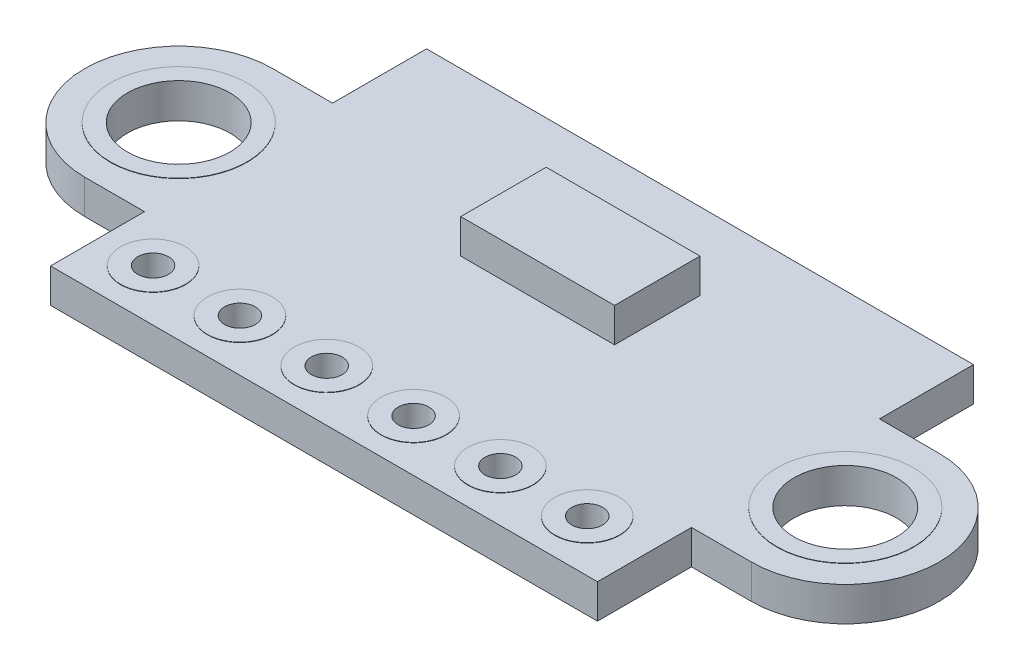
SolidWorks part; units mm, degrees
ref_plane "Front" through (0, 0, 0) normal (0, 0, 1) x (1, 0, 0)
ref_plane "Top" through (0, 0, 0) normal (0, 1, 0) x (1, 0, 0)
ref_plane "Right" through (0, 0, 0) normal (1, 0, 0) x (0, 0, -1)
sketch "Эскиз1" plane through (0, 0, 0) normal (0, 1, 0) x (1, 0, 0)
  line L0 (-38.6022, 0) -> (38.6022, 0) construction
  line L1 (8, -5.5) -> (-8, -5.5)
  line L2 (8, -5.5) -> (8, 5.5) construction
  line L3 (8, 5.5) -> (-8, 5.5)
  line L4 (-8, -5.5) -> (-8, 5.5) construction
  line L5 (8, -5.5) -> (-8, 5.5) construction
  line L6 (8, 5.5) -> (-8, -5.5) construction
  line L7 (-8, 5.5) -> (-8, 2.75)
  line L8 (0, -16.638) -> (0, 16.638) construction
  line L9 (-9.75, 2.75) -> (-8, 2.75)
  line L10 (-8, -5.5) -> (-8, -2.75)
  line L11 (-9.75, -2.75) -> (-8, -2.75)
  line L12 (9.75, -2.75) -> (8, -2.75)
  line L13 (8, -5.5) -> (8, -2.75)
  line L14 (8, 5.5) -> (8, 2.75)
  line L15 (9.75, 2.75) -> (8, 2.75)
  circle A0 centre (-9.75, 0) radius 1.5
  arc A1 (-9.75, 2.75) -> (-9.75, -2.75) centre (-9.75, 0) ccw
  circle A2 centre (9.75, 0) radius 1.5
  arc A3 (9.75, 2.75) -> (9.75, -2.75) centre (9.75, 0) cw
  circle A4 centre (-9.75, 0) radius 2
  circle A5 centre (9.75, 0) radius 2
  circle A6 centre (-6.5, -4) radius 0.45
  circle A7 centre (-6.5, -4) radius 0.95
  circle A8 centre (-3.96, -4) radius 0.95
  circle A9 centre (-3.96, -4) radius 0.45
  circle A10 centre (-1.42, -4) radius 0.95
  circle A11 centre (-1.42, -4) radius 0.45
  circle A12 centre (1.12, -4) radius 0.95
  circle A13 centre (1.12, -4) radius 0.45
  circle A14 centre (3.66, -4) radius 0.95
  circle A15 centre (3.66, -4) radius 0.45
  circle A16 centre (6.2, -4) radius 0.95
  circle A17 centre (6.2, -4) radius 0.45
  point P0 (0, 0)
  point P9 (0, 0)
  point P13 (0, 0)
  point P18 (-12.5, 0)
  point P25 (12.5, 0)
  dimension "D1" = 3
  dimension "D2" = 2.75
  dimension "D6" = 4
  dimension "D7" = 0.9
  dimension "D8" = 1.9
  dimension "D3" = 16
  dimension "D4" = 11
  dimension "D5" = 25
  dimension "D9" = 1.5
  dimension "D10" = 1.5
  dimension "D12" = 2.54
  dimension "D11" = 6
extrude "Бобышка-Вытянуть1" add sketch "Эскиз1" along normal blind 1 contours A0 | A2 | A6 | A9 | A11 | A13 | A15 | A17 | L7 L9 A1 L11 L10 L1 L13 L12 A3 L15 L14 L3 region at (-9.75, 0, 0) region at (9.75, 0, 0) region at (-6.5, 0, 4) region at (-3.96, 0, 4) region at (-1.42, 0, 4) region at (1.12, 0, 4) region at (3.66, 0, 4) region at (6.2, 0, 4)
extrude "Бобышка-Вытянуть2" add sketch "Эскиз1<3>" along normal blind 1.02 from offset 0.01 contours A4 A0 | A7 A6 | A8 A9 | A10 A11 | A12 A13 | A14 A15 | A16 A17 | A5 A2 region at (-11.6934, 0, 0) region at (7.8066, 0, 0) region at (-7.4231, 0, 4) region at (-4.8831, 0, 4) region at (-2.3431, 0, 4) region at (0.1969, 0, 4) region at (2.7369, 0, 4) region at (5.2769, 0, 4) offset against normal yes
sketch "Эскиз1<3>" plane through (0, 0, 0) normal (0, 1, 0) x (1, 0, 0) same geometry as "Эскиз1"
sketch "Эскиз2" plane through (0, 1, 0) normal (0, 1, 0) x (1, 0, 0)
  line L0 (8, 5.5) -> (-8, 5.5) construction
  line L1 (2.25, 0.75) -> (-2.25, 0.75)
  line L2 (2.25, 0.75) -> (2.25, 3.25)
  line L3 (2.25, 3.25) -> (-2.25, 3.25)
  line L4 (-2.25, 0.75) -> (-2.25, 3.25)
  line L5 (2.25, 0.75) -> (-2.25, 3.25) construction
  line L6 (2.25, 3.25) -> (-2.25, 0.75) construction
  point P0 (0, 2)
  point P5 (0, 0)
  dimension "D1" = 4.5
  dimension "D2" = 2.5
  dimension "D3" = 2.25
extrude "Бобышка-Вытянуть3" add sketch "Эскиз2" along normal blind 1
sketch "Эскиз3" plane through (0, 0, 0) normal (0, -1, 0) x (1, 0, 0)
  line L0 (8, -5.5) -> (-8, -5.5) construction
  line L1 (-6, 2.3) -> (-4.4, 2.3)
  line L2 (-6, 2.3) -> (-6, 1.45)
  line L3 (-6, 1.45) -> (-4.4, 1.45)
  line L4 (-4.4, 2.3) -> (-4.4, 1.45)
  line L5 (-5.2, 1.45) -> (-5.2, 2.3) construction
  line L6 (-6, 1.875) -> (-4.4, 1.875) construction
  line L7 (-7, -0.5) -> (-4, -0.5)
  line L8 (-7, -0.5) -> (-7, -2)
  line L9 (-7, -2) -> (-4, -2)
  line L10 (-4, -0.5) -> (-4, -2)
  line L11 (-5.5, -2) -> (-5.5, -0.5) construction
  line L12 (-7, -1.25) -> (-4, -1.25) construction
  line L13 (-3, -0.5) -> (-1.2, -0.5)
  line L14 (-3, -0.5) -> (-3, 2.5)
  line L15 (-3, 2.5) -> (-1.2, 2.5)
  line L16 (-1.2, -0.5) -> (-1.2, 2.5)
  line L17 (-2.1, 2.5) -> (-2.1, -0.5) construction
  line L18 (-3, 1) -> (-1.2, 1) construction
  line L19 (0.5, 1.5) -> (2.5, 1.5)
  line L20 (0.5, 1.5) -> (0.5, 0.3)
  line L21 (0.5, 0.3) -> (2.5, 0.3)
  line L22 (2.5, 1.5) -> (2.5, 0.3)
  line L23 (1.5, 0.3) -> (1.5, 1.5) construction
  line L24 (0.5, 0.9) -> (2.5, 0.9) construction
  line L25 (4.65, 0.1) -> (5.5, 0.1)
  line L26 (4.65, 0.1) -> (4.65, -1.5)
  line L27 (4.65, -1.5) -> (5.5, -1.5)
  line L28 (5.5, 0.1) -> (5.5, -1.5)
  line L29 (5.075, -1.5) -> (5.075, 0.1) construction
  line L30 (4.65, -0.7) -> (5.5, -0.7) construction
  line L31 (6.15, 0.1) -> (7, 0.1)
  line L32 (6.15, 0.1) -> (6.15, -1.5)
  line L33 (6.15, -1.5) -> (7, -1.5)
  line L34 (7, 0.1) -> (7, -1.5)
  line L35 (6.575, -1.5) -> (6.575, 0.1) construction
  line L36 (6.15, -0.7) -> (7, -0.7) construction
  line L37 (-2.115, -2.9) -> (-1.265, -2.9)
  line L38 (-2.115, -2.9) -> (-2.115, -4.5)
  line L39 (-2.115, -4.5) -> (-1.265, -4.5)
  line L40 (-1.265, -2.9) -> (-1.265, -4.5)
  line L41 (-1.69, -4.5) -> (-1.69, -2.9) construction
  line L42 (-2.115, -3.7) -> (-1.265, -3.7) construction
  line L43 (-0.425, -2.9) -> (0.425, -2.9)
  line L44 (-0.425, -2.9) -> (-0.425, -4.5)
  line L45 (-0.425, -4.5) -> (0.425, -4.5)
  line L46 (0.425, -2.9) -> (0.425, -4.5)
  line L47 (0, -4.5) -> (0, -2.9) construction
  line L48 (-0.425, -3.7) -> (0.425, -3.7) construction
  line L49 (1.265, -2.9) -> (2.115, -2.9)
  line L50 (1.265, -2.9) -> (1.265, -4.5)
  line L51 (1.265, -4.5) -> (2.115, -4.5)
  line L52 (2.115, -2.9) -> (2.115, -4.5)
  line L53 (1.69, -4.5) -> (1.69, -2.9) construction
  line L54 (1.265, -3.7) -> (2.115, -3.7) construction
  line L55 (-8, -5.5) -> (-8, -2.75) construction
  line L56 (-8, 5.5) -> (-8, 2.75) construction
  line L57 (8, 5.5) -> (-8, 5.5) construction
  line L58 (8, -5.5) -> (8, -2.75) construction
  line L59 (8, 5.5) -> (8, 2.75) construction
  point P36 (0, 0)
  point P43 (-5.2, 1.8008)
  point P46 (5.4261, -0.9968)
  point P88 (5.075, -0.7)
  point P96 (-5.2, 1.875)
  point P102 (-1.69, -3.7)
  point P123 (0, -3.7)
  point P129 (-5.5, -1.25)
  point P158 (-2.1, 1)
  point P160 (6.575, -0.7)
  point P167 (1.69, -3.7)
  point P179 (1.5, 0.9)
  dimension "D1" = 1.6
  dimension "D2" = 0.85
  dimension "D3" = 1.69
  dimension "D4" = 1.69
  dimension "D5" = 1
  dimension "D6" = 3
  dimension "D7" = 1.5
  dimension "D8" = 3.5
  dimension "D9" = 1
  dimension "D10" = 1.8
  dimension "D11" = 3
  dimension "D12" = 2
  dimension "D13" = 3.2
  dimension "D14" = 1.5
  dimension "D15" = 4
  dimension "D16" = 1
  dimension "D17" = 1.2
  dimension "D18" = 2
  dimension "D19" = 4
  dimension "D20" = 5.5
  dimension "D21" = 3
  dimension "D22" = 5
extrude "Бобышка-Вытянуть4" add sketch "Эскиз3" along normal blind 0.8 contours L4 L1 L2 L3 | L40 L37 L38 L39 | L46 L43 L44 L45 | L52 L49 L50 L51 region at (-5.2, 0, 1.875) region at (-1.69, 0, -3.7) region at (0, 0, -3.7) region at (1.69, 0, -3.7)
extrude "Бобышка-Вытянуть5" add sketch "Эскиз3<3>" along normal blind 0.5 contours L34 L31 L32 L33 | L28 L25 L26 L27 | L13 L16 L15 L14 region at (-2.1, 0, 1) region at (5.075, 0, -0.7) region at (6.575, 0, -0.7)
sketch "Эскиз3<3>" plane through (0, 0, 0) normal (0, -1, 0) x (1, 0, 0) same geometry as "Эскиз3"
extrude "Бобышка-Вытянуть6" add sketch "Эскиз3<4>" along normal blind 1 contours L10 L7 L8 L9 | L22 L19 L20 L21 region at (-5.5, 0, -1.25) region at (1.5, 0, 0.9)
sketch "Эскиз3<4>" plane through (0, 0, 0) normal (0, -1, 0) x (1, 0, 0) same geometry as "Эскиз3"
equation "\"D3@Эскиз2\"=11-8.75"
